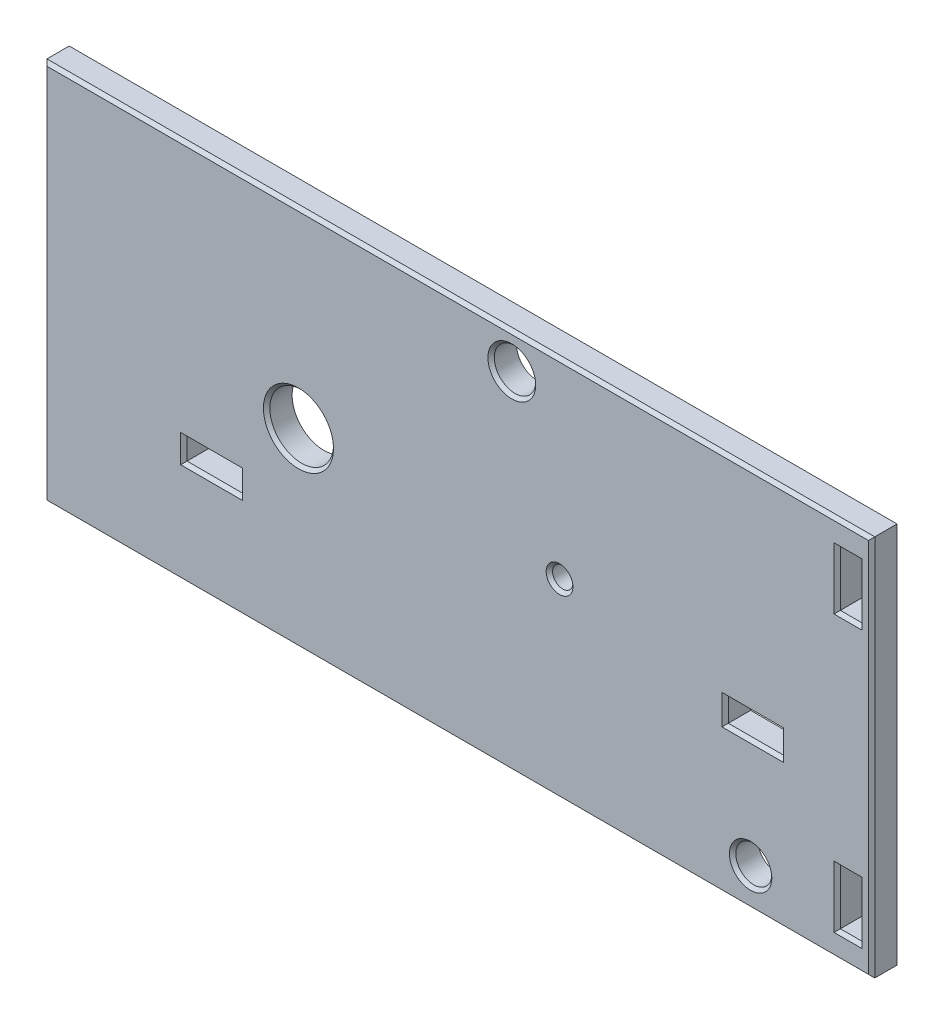
SolidWorks part; units mm, degrees
ref_plane "Front Plane" through (0, 0, 0) normal (0, 0, 1) x (1, 0, 0)
ref_plane "Top Plane" through (0, 0, 0) normal (0, 1, 0) x (1, 0, 0)
ref_plane "Right Plane" through (0, 0, 0) normal (1, 0, 0) x (0, 0, -1)
sketch "Sketch1" plane through (0, 0, 0) normal (0, 0, 1) x (1, 0, 0)
  line L0 (-55.3, -10.3) -> (-55.3, -13.7)
  line L1 (-86, -30) -> (44, -30)
  line L2 (-86, -30) -> (-86, 30)
  line L3 (-86, 30) -> (44, 30)
  line L4 (44, -30) -> (44, 30)
  line L5 (-64, -10.3) -> (-55.3, -10.3)
  line L6 (-64, -10.3) -> (-64, -13.7)
  line L7 (-64, -13.7) -> (-55.3, -13.7)
  line L13 (29.7, -5) -> (21, -5) construction
  line L14 (-55.3, -12) -> (-64, -12) construction
  line L15 (-59.65, -10.3) -> (-59.65, -13.7) construction
  line L16 (40.3, 26) -> (40.3, 17.3) construction
  line L17 (38.6, 26) -> (42, 26)
  line L18 (38.6, 26) -> (38.6, 17.3)
  line L19 (38.6, 17.3) -> (42, 17.3)
  line L20 (42, 26) -> (42, 17.3)
  line L21 (38.6, -17.3) -> (42, -17.3)
  line L22 (38.6, -17.3) -> (38.6, -26)
  line L23 (38.6, -26) -> (42, -26)
  line L24 (42, -17.3) -> (42, -26)
  line L25 (42, 21.65) -> (38.6, 21.65) construction
  line L26 (40.3, -17.3) -> (40.3, -26) construction
  line L27 (42, -21.65) -> (38.6, -21.65) construction
  line L28 (21, -3.15) -> (29.7, -3.15)
  line L29 (21, -3.15) -> (21, -6.85)
  line L30 (21, -6.85) -> (29.7, -6.85)
  line L31 (29.7, -3.15) -> (29.7, -6.85)
  line L32 (25.35, -6.85) -> (25.35, -3.15) construction
  circle A2 centre (-46, 0) radius 5
  circle A3 centre (-12.5, 24.5) radius 3.25
  circle A4 centre (25, -24) radius 2.83
  circle A5 centre (-5, 0) radius 1.6
  point P1 (0, 0)
  point P24 (-86, 0)
  dimension "D10" = 6.5
  dimension "D14" = 5.66
  dimension "D21" = 10
  dimension "D2" = 60
  dimension "D4" = 130
  dimension "D6" = 8.7
  dimension "D8" = 3.4
  dimension "D12" = 111
  dimension "D19" = 24.5
  dimension "D13" = 24
  dimension "D5" = 40
  dimension "D7" = 33.5
  dimension "D9" = 7.5
  dimension "D11" = 26.35
  dimension "D15" = 126.3
  dimension "D17" = 21.65
  dimension "D18" = 21.65
  dimension "D16" = 85
  dimension "D3" = 5
  dimension "D20" = 12
extrude "Boss-Extrude1" add sketch "Sketch1" along normal mid plane 4
sketch "Sketch2" plane through (0, 0, 2) normal (0, 0, 1) x (1, 0, 0)
  line L0 (40.3, 26) -> (40.3, 17.3) construction
  line L1 (42, 21.65) -> (38.6, 21.65) construction
  line L2 (40.3, -17.3) -> (40.3, -26) construction
  line L3 (42, -17.3) -> (38.6, -17.3) construction
  line L4 (38.6, -26) -> (42, -26) construction
  line L5 (38.6, -21.65) -> (42, -21.65) construction
  line L6 (38.6, -17.3) -> (38.6, -26) construction
  line L7 (42, -26) -> (42, -17.3) construction
sketch "Sketch4" plane through (0, 0, -2) normal (0, 0, -1) x (-1, 0, 0)
  line L0 (59.65, -10.3) -> (59.65, -13.7) construction
  line L1 (55.3, -12) -> (64, -12) construction
  line L2 (-29.7, -5) -> (-21, -5) construction
  line L3 (-29.7, -6.85) -> (-29.7, -3.15) construction
  line L4 (-21, -3.15) -> (-21, -6.85) construction
  line L5 (-25.35, -3.15) -> (-25.35, -6.85) construction
  line L6 (-29.7, -3.15) -> (-21, -3.15) construction
  line L7 (-21, -6.85) -> (-29.7, -6.85) construction
chamfer "Chamfer1" distance 0.5 angle 45 24 edges at (40.3, -26, 2) (42, -21.65, 2) (40.3, -17.3, 2) (38.6, -21.65, 2) (-3.4, 0, 2) (27.83, -24, 2) (-41, 0, 2) (-9.25, 24.5, 2) (-59.65, -13.7, 2) (-55.3, -12, 2) (-59.65, -10.3, 2) (-64, -12, 2) (-21, -30, 2) (-86, 0, 2) (-21, 30, 2) (44, 0, 2) (25.35, -6.85, 2) (29.7, -5, 2) (25.35, -3.15, 2) (21, -5, 2) (40.3, 17.3, 2) (42, 21.65, 2) (40.3, 26, 2) (38.6, 21.65, 2)
equation "\"padding\"=4"
equation "\"hole_width\"=3.4"
equation "\"hole_height\"=8.7"
equation "\"back_boost\"= 7"
equation "\"D5@Sketch1\"=33+\"back_boost\""
equation "\"D12@Sketch1\"=104+\"back_boost\""
equation "\"D15@Sketch1\"=119.30mm+\"back_boost\""
equation "\"D11@Sketch1\"=\"back_boost\"+19.35mm"
equation "\"D4@Sketch1\"=\"back_boost\"+123.00mm"
equation "\"pin_hole_height\"=9"
equation "\"pin_hole_width\"=4.2"
